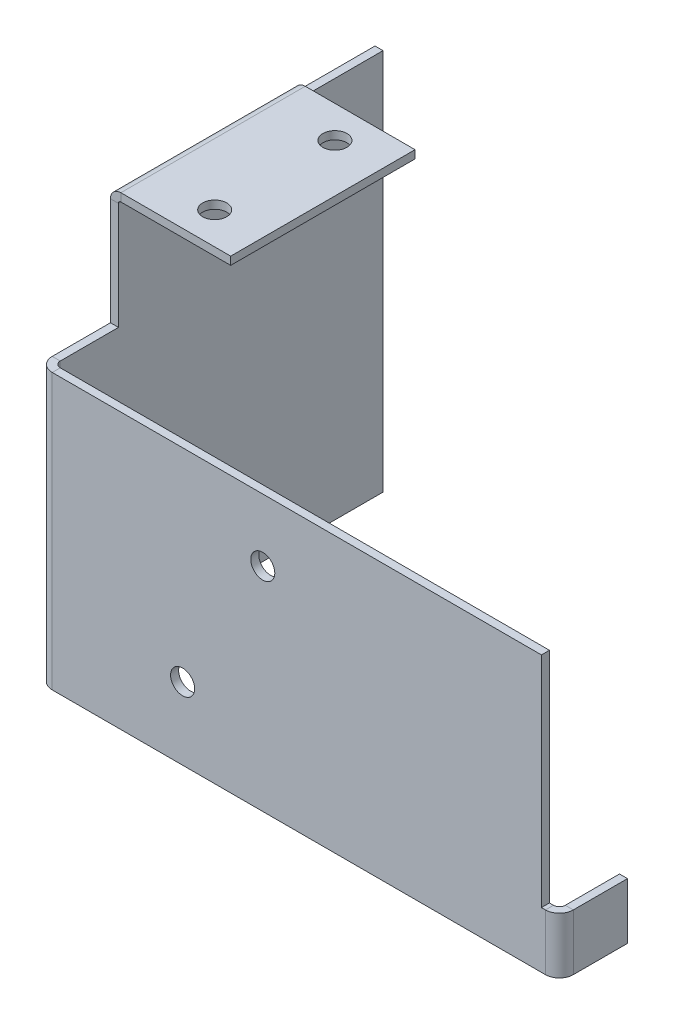
SolidWorks part; units mm, degrees
note: The reader was unsure of these and kept them because the rebuilt part matched: flange length of "Edge-Flange1", "Edge-Flange3", "Edge-Flange4".
material "1023 Carbon Steel Sheet (SS)"
ref_plane "Front Plane" through (0, 0, 0) normal (0, 0, 1) x (1, 0, 0)
ref_plane "Top Plane" through (0, 0, 0) normal (0, 1, 0) x (1, 0, 0)
ref_plane "Right Plane" through (0, 0, 0) normal (1, 0, 0) x (0, 0, -1)
sketch "Sketch1" plane through (0, 0, 0) normal (0, 1, 0) x (1, 0, 0)
  line L1 (0, 0) -> (-15, 0)
  line L2 (0, 0) -> (0, -23)
  line L3 (0, -23) -> (-15, -23)
  line L4 (-15, 0) -> (-15, -23)
  dimension "D1" = 15
  dimension "D2" = 23
base flange "Base-Flange1" sketch "Sketch1" thickness 1 reverse thickness direction no parameters "D1"=0.7366
edge flange "Edge-Flange1" sketch "Sketch8" flange angle 90 flange length 49 flange position material inside bend radius 0.3 thickness 1 parameters "D6"=10
sketch "Sketch8" plane through (-15, -1, 0) normal (1, 0, 0) x (0, 0, 1)
  line L2 (0, 0) -> (0, 48)
  line L3 (0, 48) -> (23, 48)
  line L4 (23, 48) -> (23, 0)
  line L5 (23, 0) -> (0, 0) construction
  line L6 (23, 0) -> (0, 0)
bend "EdgeBend1" bend radius 0.3 bend angle 90 parameters "D5"=1
sketch "Sketch10" plane through (-15, 0, 0) normal (-1, 0, 0) x (0, 0, 1)
  line L1 (0, -49) -> (-10, -49)
  line L2 (0, -49) -> (0, -1.3)
  line L3 (0, -1.3) -> (-10, -1.3)
  line L4 (-10, -49) -> (-10, -1.3)
  line L5 (23, -1.3) -> (0, -1.3) construction
  line L6 (23, -1.3) -> (23, -49) construction
  dimension "D1" = 33
extrude "Boss-Extrude2" add sketch "Sketch10" against normal up to surface (1 mm away) up to face at (-14, -25.15, 11.5)
sketch "Sketch15" plane through (0, 0, 23) normal (0, 0, 1) x (1, 0, 0)
  line L0 (-14, -1.3) -> (-14, -49) construction
  line L1 (-15, -49) -> (-14, -49)
  line L2 (-15, -49) -> (-15, -14.7)
  line L3 (-15, -14.7) -> (-14, -14.7)
  line L4 (-14, -49) -> (-14, -14.7)
  dimension "D1" = 34.3
extrude "Boss-Extrude3" add sketch "Sketch15" along normal blind 9
edge flange "Edge-Flange3" sketch "Sketch18" flange angle 90 flange length 65 flange position material inside bend radius 0.7366 thickness 1 parameters "D6"=10
sketch "Sketch18" plane through (-14, 0, 32) normal (0, 0, 1) x (0, -1, 0)
  line L2 (14.7, 0) -> (14.7, 64)
  line L3 (14.7, 64) -> (49, 64)
  line L4 (49, 64) -> (49, 0)
  line L7 (49, 0) -> (14.7, 0) construction
  line L8 (49, 0) -> (14.7, 0)
bend "EdgeBend3" bend radius 0.7366 bend angle 90 parameters "D5"=2
edge flange "Edge-Flange4" sketch "Sketch30" flange angle 90 flange length 8.5 flange position material inside bend radius 0.7366 thickness 1 parameters "D6"=10
sketch "Sketch30" plane through (50, 0, 31) normal (1, 0, 0) x (0, -1, 0)
  line L0 (49, 0) -> (14.7, 0) construction
  line L1 (49, 0) -> (42, 0)
  line L2 (42, 0) -> (42, 7.5)
  line L3 (42, 7.5) -> (49, 7.5)
  line L4 (49, 7.5) -> (49, 0)
  line L6 (49, 0.7366) -> (49, 41) construction
  dimension "D1" = 7
bend "EdgeBend4" bend radius 0.7366 bend angle 90 parameters "D5"=3
sketch "Sketch31" plane through (0, 0, 32) normal (0, 0, 1) x (1, 0, 0)
  line L0 (-15, -1.3) -> (-15, -49) construction
  line L1 (-13.2634, -49) -> (48.2634, -49) construction
  line L2 (-15, -49) -> (-15, -1.3) construction
  circle A0 centre (3, -40) radius 1.5
  circle A1 centre (13, -22.5) radius 1.5
  dimension "D3" = 3
  dimension "D1" = 18
  dimension "D2" = 9
  dimension "D4" = 28
  dimension "D5" = 26.5
extrude "Cut-Extrude1" cut sketch "Sketch31" against normal through all
sketch "Sketch32" plane through (0, 0, 0) normal (0, 1, 0) x (1, 0, 0)
  line L0 (0, -23) -> (0, 0) construction
  line L5 (-6, -4) -> (-6, -19) construction
  line L6 (-6, -11.5) -> (0, -11.5) construction
  line L7 (-15, 0) -> (-15, 10) construction
  circle A0 centre (-6, -4) radius 1.5
  circle A1 centre (-6, -19) radius 1.5
  point P4 (0, -11.5)
  dimension "D2" = 3
  dimension "D1" = 9
  dimension "D3" = 15
extrude "Cut-Extrude2" cut sketch "Sketch32" against normal blind 10
sketch "Bend-Lines1" [suppressed] plane through (0, 0, 0) normal (0, 1, 0) x (1, 0, 0)
sketch "Bounding-Box1" [suppressed] plane through (0, 0, 0) normal (0, 1, 0) x (1, 0, 0)
sheet metal parameters "Sheet-Metal1" thickness 1 parameters "D1"=0.7366
flat pattern "Flat-Pattern1" [suppressed]
sketch "Bend-Lines2" plane through (0, 0, 0) normal (0, 1, 0) x (1, 0, 0)
sketch3d "Bounding-Box2" [suppressed]
  line L0 (0, 0, 0) -> (15, 0, 0) construction
  line L1 (0, -10, 0) -> (15, -10, 0) construction
  line L2 (0, 0, 0) -> (0, -10, 0) construction
  line L3 (15, 0, 0) -> (15, -10, 0) construction
sheet metal parameters "Sheet-Metal2" thickness 1 parameters "D1"=0.7366
flat pattern "Flat-Pattern1" [suppressed]
sketch "Bend-Lines2" plane through (0, 0, 0) normal (0, 1, 0) x (1, 0, 0)
  line L0 (-14.3283, 0) -> (-14.3283, -23) construction
  line L1 (-14.3283, 0) -> (-14.3283, -23) construction
sketch3d "Bounding-Box2" [suppressed]
  line L0 (0, 0, 0) -> (-62.6566, 0, 0) construction
  line L1 (0, -23, 0) -> (-62.6566, -23, 0) construction
  line L2 (0, 0, 0) -> (0, -23, 0) construction
  line L3 (-62.6566, 0, 0) -> (-62.6566, -23, 0) construction
bend of the flat pattern "Flatten-<EdgeBend1>1"
sketch "Sketch10-1" [suppressed] plane through (-13.6566, 0, 0) normal (0, 1, 0) x (0, 0, 1)
  line L0 (0, 0) -> (23, 0) construction
  line L1 (0, -49) -> (-18.0976, -49)
  line L2 (0, -49) -> (0, -1)
  line L3 (0, -1) -> (-18.0976, -1)
  line L4 (-18.0976, -49) -> (-18.0976, -1)
  dimension "D1" = 1
sheet metal parameters "Sheet-Metal3" thickness 1 parameters "D1"=0.7366
flat pattern "Flat-Pattern1" [suppressed]
sketch "Bend-Lines2" plane through (0, 0, 0) normal (0, 1, 0) x (1, 0, 0)
  line L0 (-14.3283, 0) -> (-14.3283, -23) construction
  line L1 (-14.3283, 0) -> (-14.3283, -23) construction
sketch3d "Bounding-Box2" [suppressed]
  line L0 (0, 10, 0) -> (-62.6566, 10, 0) construction
  line L1 (0, -23, 0) -> (-62.6566, -23, 0) construction
  line L2 (0, 10, 0) -> (0, -23, 0) construction
  line L3 (-62.6566, 10, 0) -> (-62.6566, -23, 0) construction
bend of the flat pattern "Flatten-<EdgeBend1>1"
sketch "Sketch10-1" [suppressed] plane through (-13.6566, 0, 0) normal (0, 1, 0) x (0, 0, 1)
  line L1 (0, -49) -> (-10, -49)
  line L2 (0, -49) -> (0, -1.3)
  line L3 (0, -1.3) -> (-10, -1.3)
  line L4 (-10, -49) -> (-10, -1.3)
  line L6 (23, 13.6566) -> (23, -49) construction
  dimension "D1" = 33
sheet metal parameters "Sheet-Metal5" thickness 1 parameters "D1"=0.7366
flat pattern "Flat-Pattern1"
sketch "Bend-Lines2" plane through (0, 0, 0) normal (0, 1, 0) x (1, 0, 0)
  line L0 (-14.3283, 0) -> (-14.3283, -23) construction
  line L1 (-14.3283, 0) -> (-14.3283, -23) construction
sketch3d "Bounding-Box2" [suppressed]
  line L0 (0, 0, 0) -> (-62.6566, 0, 0) construction
  line L1 (0, -23, 0) -> (-62.6566, -23, 0) construction
  line L2 (0, 0, 0) -> (0, -23, 0) construction
  line L3 (-62.6566, 0, 0) -> (-62.6566, -23, 0) construction
bend of the flat pattern "Flatten-<EdgeBend1>1"
sheet metal parameters "Sheet-Metal6" thickness 1 parameters "D1"=0.7366
flat pattern "Flat-Pattern1"
sketch "Bend-Lines2" plane through (0, 0, 0) normal (0, 1, 0) x (1, 0, 0)
  line L0 (-14.3283, 0) -> (-14.3283, -23) construction
  line L1 (-14.3283, 0) -> (-14.3283, -23) construction
  line L2 (-28.3566, 8.2346) -> (-62.6566, 8.2346) construction
  line L3 (-28.3566, 8.2346) -> (-62.6566, 8.2346) construction
sketch3d "Bounding-Box2" [suppressed]
  line L0 (-62.6566, -23, 0) -> (-62.6566, 72.4692, 0) construction
  line L1 (0, -23, 0) -> (0, 72.4692, 0) construction
  line L2 (-62.6566, -23, 0) -> (0, -23, 0) construction
  line L3 (-62.6566, 72.4692, 0) -> (0, 72.4692, 0) construction
bend of the flat pattern "Flatten-<EdgeBend1>1"
bend of the flat pattern "Flatten-<EdgeBend3>1"
sheet metal parameters "Sheet-Metal7" thickness 1 parameters "D1"=0.7366
flat pattern "Flat-Pattern1" [suppressed]
sketch "Bend-Lines2" plane through (0, 0, 0) normal (0, 1, 0) x (1, 0, 0)
  line L0 (-14.3283, 0) -> (-14.3283, -23) construction
  line L1 (-14.3283, 0) -> (-14.3283, -23) construction
  line L2 (-62.6566, -31.2346) -> (-28.3566, -31.2346) construction
  line L3 (-62.6566, -31.2346) -> (-28.3566, -31.2346) construction
  line L4 (-62.6566, -94.7039) -> (-55.6566, -94.7039) construction
  line L5 (-62.6566, -94.7039) -> (-55.6566, -94.7039) construction
sketch3d "Bounding-Box2" [suppressed]
  line L0 (-62.6566, -102.4385, 0) -> (-62.6566, 10, 0) construction
  line L1 (0, -102.4385, 0) -> (0, 10, 0) construction
  line L2 (-62.6566, -102.4385, 0) -> (0, -102.4385, 0) construction
  line L3 (-62.6566, 10, 0) -> (0, 10, 0) construction
bend of the flat pattern "Flatten-<EdgeBend1>1"
bend of the flat pattern "Flatten-<EdgeBend3>1"
bend of the flat pattern "Flatten-<EdgeBend4>1"
sketch "Sketch10-2" [suppressed] plane through (-13.6566, 0, 0) normal (0, 1, 0) x (0, 0, 1)
  line L1 (0, -49) -> (-10, -49)
  line L2 (0, -49) -> (0, -1.3)
  line L3 (0, -1.3) -> (-10, -1.3)
  line L4 (-10, -49) -> (-10, -1.3)
  line L6 (23, 13.6566) -> (23, -14.7) construction
  dimension "D1" = 33
sheet metal parameters "Sheet-Metal8" thickness 1 parameters "D1"=0.7366
flat pattern "Flat-Pattern1" [suppressed]
sketch "Bend-Lines2" plane through (0, 0, 0) normal (0, 1, 0) x (1, 0, 0)
  line L0 (-14.3283, 0) -> (-14.3283, -23) construction
  line L1 (-14.3283, 0) -> (-14.3283, -23) construction
  line L2 (-62.6566, -31.2346) -> (-28.3566, -31.2346) construction
  line L3 (-62.6566, -31.2346) -> (-28.3566, -31.2346) construction
  line L4 (-62.6566, -94.7039) -> (-55.6566, -94.7039) construction
  line L5 (-62.6566, -94.7039) -> (-55.6566, -94.7039) construction
sketch3d "Bounding-Box2" [suppressed]
  line L0 (-62.6566, -102.4385, 0) -> (-62.6566, 10, 0) construction
  line L1 (0, -102.4385, 0) -> (0, 10, 0) construction
  line L2 (-62.6566, -102.4385, 0) -> (0, -102.4385, 0) construction
  line L3 (-62.6566, 10, 0) -> (0, 10, 0) construction
bend of the flat pattern "Flatten-<EdgeBend1>1"
bend of the flat pattern "Flatten-<EdgeBend3>1"
bend of the flat pattern "Flatten-<EdgeBend4>1"
sketch "Sketch10-2" [suppressed] plane through (-13.6566, 0, 0) normal (0, 1, 0) x (0, 0, 1)
  line L1 (0, -49) -> (-10, -49)
  line L2 (0, -49) -> (0, -1.3)
  line L3 (0, -1.3) -> (-10, -1.3)
  line L4 (-10, -49) -> (-10, -1.3)
  line L6 (23, 13.6566) -> (23, -14.7) construction
  dimension "D1" = 33
sheet metal parameters "Sheet-Metal9" thickness 1 parameters "D1"=0.7366
flat pattern "Flat-Pattern1" [suppressed]
sketch "Bend-Lines2" plane through (0, 0, 0) normal (0, 1, 0) x (1, 0, 0)
  line L0 (-14.3283, 0) -> (-14.3283, -23) construction
  line L1 (-14.3283, 0) -> (-14.3283, -23) construction
  line L2 (-62.6566, -31.2346) -> (-28.3566, -31.2346) construction
  line L3 (-62.6566, -31.2346) -> (-28.3566, -31.2346) construction
  line L4 (-62.6566, -94.7039) -> (-55.6566, -94.7039) construction
  line L5 (-62.6566, -94.7039) -> (-55.6566, -94.7039) construction
sketch3d "Bounding-Box2" [suppressed]
  line L0 (-62.6566, -102.4385, 0) -> (-62.6566, 10, 0) construction
  line L1 (0, -102.4385, 0) -> (0, 10, 0) construction
  line L2 (-62.6566, -102.4385, 0) -> (0, -102.4385, 0) construction
  line L3 (-62.6566, 10, 0) -> (0, 10, 0) construction
bend of the flat pattern "Flatten-<EdgeBend1>1"
bend of the flat pattern "Flatten-<EdgeBend3>1"
bend of the flat pattern "Flatten-<EdgeBend4>1"
sketch "Sketch10-2" plane through (-13.6566, 0, 0) normal (0, 1, 0) x (0, 0, 1)
  line L1 (0, -49) -> (-10, -49)
  line L2 (0, -49) -> (0, -1.3)
  line L3 (0, -1.3) -> (-10, -1.3)
  line L4 (-10, -49) -> (-10, -1.3)
  line L6 (23, 13.6566) -> (23, -14.7) construction
  dimension "D1" = 33
